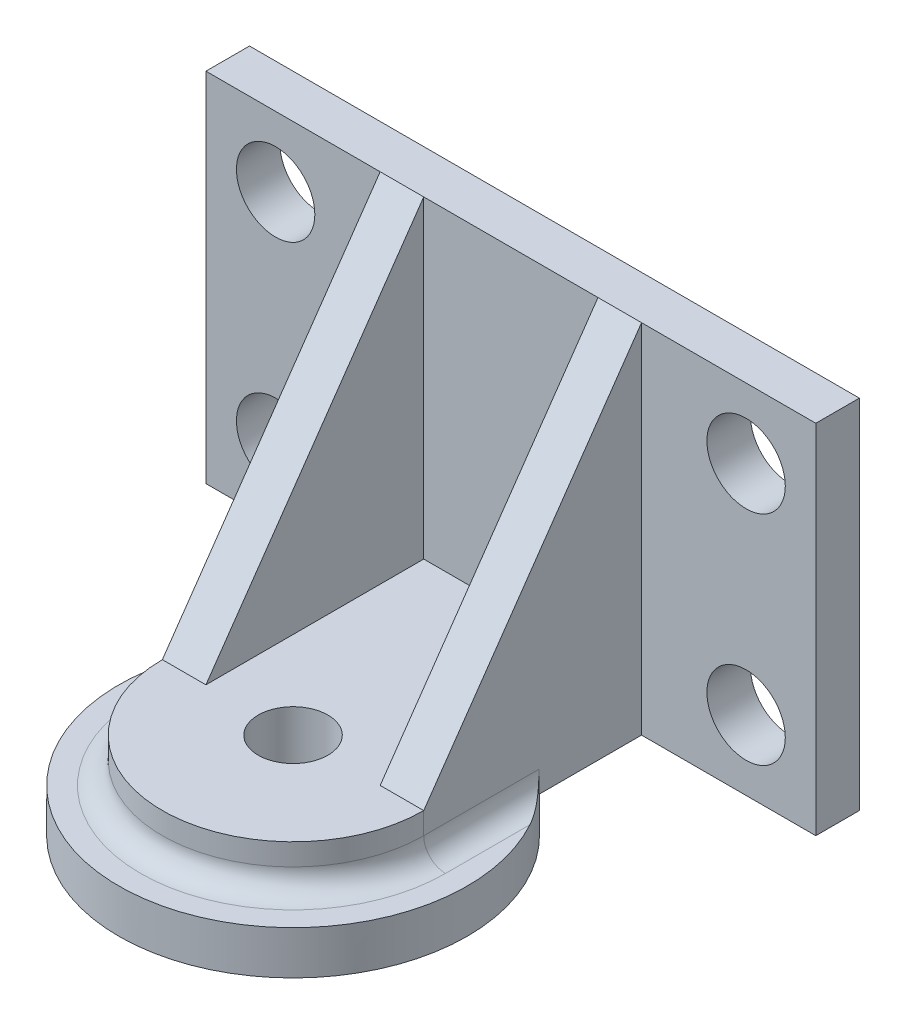
SolidWorks part; units mm, degrees
material "Plain Carbon Steel"
ref_plane "Front Plane" through (0, 0, 0) normal (0, 0, 1) x (1, 0, 0)
ref_plane "Top Plane" through (0, 0, 0) normal (0, 1, 0) x (1, 0, 0)
ref_plane "Right Plane" through (0, 0, 0) normal (1, 0, 0) x (0, 0, -1)
sketch "Sketch1" plane through (0, 0, 0) normal (0, 0, 1) x (1, 0, 0)
  line L1 (-35, 20.5) -> (35, 20.5)
  line L2 (-35, 20.5) -> (-35, -20.5)
  line L3 (-35, -20.5) -> (35, -20.5)
  line L4 (35, 20.5) -> (35, -20.5)
  circle A0 centre (-27, 12.5) radius 4.5
  circle A1 centre (-27, -12.5) radius 4.5
  circle A2 centre (27, 12.5) radius 4.5
  circle A3 centre (27, -12.5) radius 4.5
  point P4 (0, 20.5)
  point P5 (-35, 0)
  point P15 (0, 0)
  point P16 (0, 0)
  point P17 (0, 0)
  point P18 (0, 0)
  point P19 (0, 0)
  point P20 (0, 0)
  dimension "D3" = 9
  dimension "D6" = 8
  dimension "D7" = 8
  dimension "D1" = 70
  dimension "D2" = 41
  dimension "D4" = 8
  dimension "D5" = 8
extrude "Boss-Extrude1" add sketch "Sketch1" along normal blind 5
sketch "Sketch2" plane through (0, 0, 5) normal (0, 0, 1) x (1, 0, 0)
  line L0 (35, 20.5) -> (-35, 20.5) construction
  line L1 (-15, 20.5) -> (-10, 20.5)
  line L2 (-15, 20.5) -> (-15, -20.5)
  line L3 (-15, -20.5) -> (-10, -20.5)
  line L4 (-10, 20.5) -> (-10, -20.5)
  line L5 (-35, -20.5) -> (35, -20.5) construction
  line L7 (10, 20.5) -> (15, 20.5)
  line L8 (10, 20.5) -> (10, -20.5)
  line L9 (10, -20.5) -> (15, -20.5)
  line L10 (15, 20.5) -> (15, -20.5)
  dimension "D1" = 5
  dimension "D2" = 10
  dimension "D3" = 10
extrude "Boss-Extrude2" add sketch "Sketch2" along normal blind 25
sketch "Sketch5" plane through (0, -20.5, 0) normal (0, -1, 0) x (1, 0, 0)
  line L2 (-15, 30) -> (-15, 5)
  line L3 (-15, 5) -> (15, 5)
  line L4 (15, 30) -> (15, 5)
  arc A0 (15, 30) -> (-15, 30) centre (0, 30) ccw
  dimension "D1" = 15
extrude "Boss-Extrude3" add sketch "Sketch5" against normal blind 5
sketch "Sketch3" plane through (0, 0, 0) normal (1, 0, 0) x (0, 0, -1)
  line L0 (-5, 20.5) -> (-30, -15.5)
  line L1 (-30, -15.5) -> (-49.543, -15.5)
  line L2 (-49.543, -15.5) -> (-49.543, 23.9444)
  line L3 (-49.543, 23.9444) -> (-5, 23.9444)
  line L4 (-5, 23.9444) -> (-5, 20.5)
  point P7 (-45, -10.5)
extrude "Cut-Extrude2" cut sketch "Sketch3" against normal through all both and the other way through all
sketch "Sketch6" plane through (0, -20.5, 0) normal (0, -1, 0) x (1, 0, 0)
  circle A0 centre (0, 30) radius 20
  dimension "D1" = 40
extrude "Boss-Extrude4" add sketch "Sketch6" along normal blind 5
sketch "Sketch7" plane through (0, -15.5, 0) normal (0, 1, 0) x (1, 0, 0)
  circle A0 centre (0, -30) radius 4
  dimension "D1" = 8
extrude "Cut-Extrude3" cut sketch "Sketch7" against normal through all
fillet "Fillet1" radius 2.5 3 edges at (15, -20.5, 23.3856) (-15, -20.5, 23.3856) (0, -20.5, 45)
